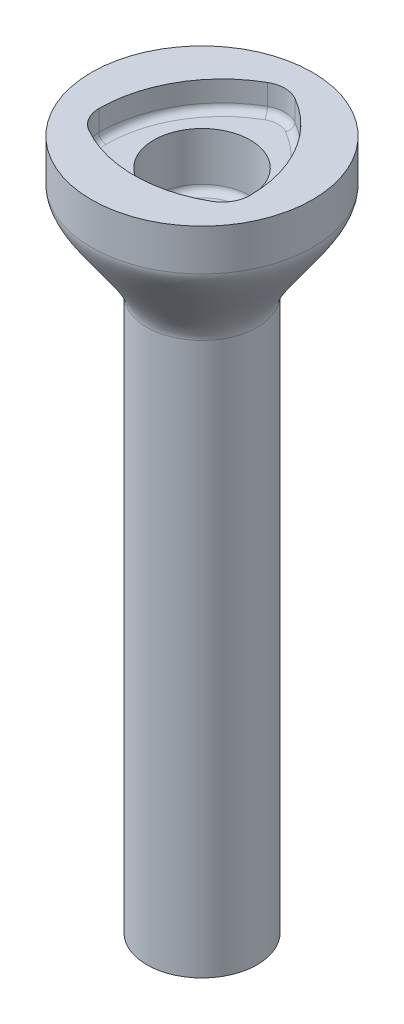
SolidWorks part; units mm, degrees
ref_plane "Front Plane" through (0, 0, 0) normal (0, 0, 1) x (1, 0, 0)
ref_plane "Top Plane" through (0, 0, 0) normal (0, 1, 0) x (1, 0, 0)
ref_plane "Right Plane" through (0, 0, 0) normal (1, 0, 0) x (0, 0, -1)
sketch "Sketch6" plane through (0, 0, 0) normal (0, 0, 1) x (1, 0, 0)
  line L0 (0, 0) -> (-8, 0)
  line L1 (-8, 0) -> (-8, 80)
  line L2 (0, 0) -> (0, 100)
  line L3 (0, 100) -> (-16, 100)
  line L4 (-16, 100) -> (-16, 94)
  line L5 (-16, 94) -> (-16, 91) construction
  line L6 (-16, 91) -> (-8, 83) construction
  line L7 (-8, 83) -> (-8, 80) construction
  spline S0 degree 3 poles (-16, 94) (-16, 91) (-8, 83) (-8, 80) knots 0 0 0 0 1 1 1 1
  dimension "D1" = 8
  dimension "D2" = 16
  dimension "D3" = 3
  dimension "D4" = 6
  dimension "D5" = 45
  dimension "D6" = 100
revolve "Revolve1" add sketch "Sketch6" angle 360 about L2
sketch "Sketch7" plane through (0, 100, 0) normal (0, 1, 0) x (1, 0, 0)
  line L1 (0, 8) -> (-6.9282, -4) construction
  line L2 (-6.9282, -4) -> (6.9282, -4) construction
  line L3 (6.9282, -4) -> (0, 8) construction
  circle A0 centre (0, 0) radius 8 construction
  arc A1 (-2, 11.4641) -> (2, 11.4641) centre (0, 8) cw
  arc A2 (10.9282, -4) -> (8.9282, -7.4641) centre (6.9282, -4) cw
  arc A3 (-8.9282, -7.4641) -> (-10.9282, -4) centre (-6.9282, -4) cw
  arc A4 (-10.9282, -4) -> (-2, 11.4641) centre (6.9282, -4) cw
  arc A5 (2, 11.4641) -> (10.9282, -4) centre (-6.9282, -4) cw
  arc A6 (8.9282, -7.4641) -> (-8.9282, -7.4641) centre (0, 8) cw
  circle A8 centre (0, 0) radius 12 construction
  dimension "D1" = 4
  dimension "D2" = 24
extrude "Cut-Extrude1" cut sketch "Sketch7" against normal blind 4
sketch "Sketch8" plane through (0, 96, 0) normal (0, 1, 0) x (1, 0, 0)
  circle A0 centre (0, 0) radius 7
  dimension "D1" = 14
extrude "Cut-Extrude2" cut sketch "Sketch8" against normal blind 8
fillet "Fillet1" radius 1 7 edges at (-10.3923, 96, 6) (-8.5359, 96, -4.9282) (0, 96, -12) (8.5359, 96, -4.9282) (10.3923, 96, 6) (0, 88, 7) (0, 96, 9.8564)
